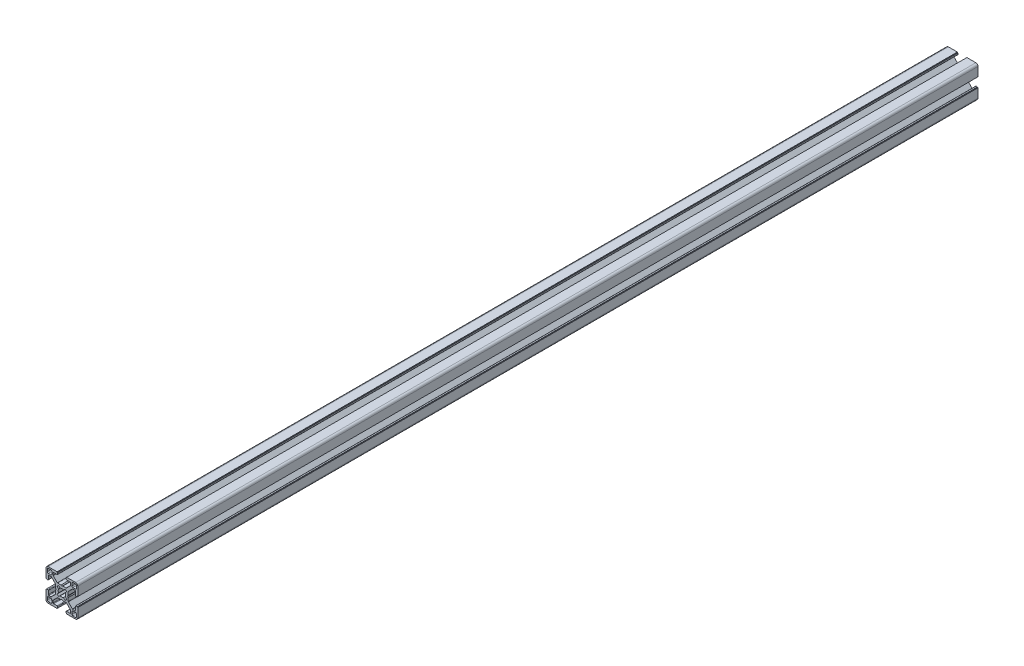
SolidWorks part; units mm, degrees
ref_plane "Front Plane" through (0, 0, 0) normal (0, 0, 1) x (1, 0, 0)
ref_plane "Top Plane" through (0, 0, 0) normal (0, 1, 0) x (1, 0, 0)
ref_plane "Right Plane" through (0, 0, 0) normal (1, 0, 0) x (0, 0, -1)
sketch "Sketch1" plane through (0, 0, 0) normal (0, 0, 1) x (1, 0, 0)
  line L0 (-15, 0) -> (15, 0) construction
  line L1 (0, -15) -> (0, 15) construction
  line L2 (-4.5, 15) -> (4.5, 15) construction
  line L3 (-4, -15) -> (4, -15) construction
  line L4 (-4.5, 15) -> (-4.5, 14.5)
  line L5 (-4.5, 14.5) -> (-4, 14.5)
  line L6 (-4, 14.5) -> (-4, 13.29)
  line L7 (-4.5, 12.79) -> (-7.7675, 12.79)
  line L8 (-8.2675, 12.29) -> (-8.2675, 10.2707)
  line L9 (-8.1211, 9.9171) -> (-4.3504, 6.1464)
  line L10 (-3.9968, 6) -> (0, 6)
  line L11 (0, 0) -> (-15, 15) construction
  line L12 (-4.5, 15) -> (-12.968, 15)
  line L14 (-12.705, 9.5135) -> (-10.5135, 9.5135)
  line L15 (-13.705, 10.5135) -> (-13.705, 12.705)
  line L16 (-12.705, 13.705) -> (-10.5135, 13.705)
  line L17 (-9.5135, 10.5135) -> (-9.5135, 12.705)
  line L18 (-13.705, 9.5135) -> (-9.5135, 13.705) construction
  line L19 (-13.705, 13.705) -> (-9.5135, 9.5135) construction
  line L20 (-3.1568, 4.5038) -> (-1.5303, 3.1477) construction
  line L21 (-4.5038, 3.1568) -> (-3.1477, 1.5303) construction
  line L22 (-6, 3.9968) -> (-6, 0)
  line L23 (-9.9171, 8.1211) -> (-6.1464, 4.3504)
  line L24 (-15, 4.5) -> (-15, 12.968)
  line L25 (-12.29, 8.2675) -> (-10.2707, 8.2675)
  line L26 (-12.79, 4.5) -> (-12.79, 7.7675)
  line L27 (-14.5, 4) -> (-13.29, 4)
  line L28 (-14.5, 4.5) -> (-14.5, 4)
  line L29 (-15, 4.5) -> (-14.5, 4.5)
  circle A0 centre (0, 0) radius 3.5
  arc A1 (-12.968, 15) -> (-15, 12.968) centre (-12.968, 12.968) ccw
  circle A2 centre (0, 0) radius 5.5 construction
  arc A3 (-10.5135, 9.5135) -> (-9.5135, 10.5135) centre (-10.5135, 10.5135) ccw
  arc A4 (-13.705, 12.705) -> (-12.705, 13.705) centre (-12.705, 12.705) cw
  arc A5 (-10.5135, 13.705) -> (-9.5135, 12.705) centre (-10.5135, 12.705) cw
  arc A6 (-12.705, 9.5135) -> (-13.705, 10.5135) centre (-12.705, 10.5135) cw
  arc A7 (-12.79, 4.5) -> (-13.29, 4) centre (-13.29, 4.5) cw
  arc A8 (-12.29, 8.2675) -> (-12.79, 7.7675) centre (-12.29, 7.7675) ccw
  arc A9 (-9.9171, 8.1211) -> (-10.2707, 8.2675) centre (-10.2707, 7.7675) ccw
  arc A10 (-6, 3.9968) -> (-6.1464, 4.3504) centre (-6.5, 3.9968) ccw
  arc A11 (-4.3504, 6.1464) -> (-3.9968, 6) centre (-3.9968, 6.5) ccw
  arc A12 (-4, 13.29) -> (-4.5, 12.79) centre (-4.5, 13.29) cw
  arc A13 (-7.7675, 12.79) -> (-8.2675, 12.29) centre (-7.7675, 12.29) ccw
  arc A14 (-8.2675, 10.2707) -> (-8.1211, 9.9171) centre (-7.7675, 10.2707) ccw
  point P4 (0, 0)
  point P8 (0, 0)
  point P13 (0, 15)
  point P15 (0, -15)
  point P16 (0, 6)
  point P23 (-11.6092, 11.6093)
  point P26 (0, 6)
  point P62 (-12.79, 4)
  point P65 (-12.79, 8.2675)
  point P68 (-10.0636, 8.2675)
  point P71 (-6, 4.2039)
  point P74 (-4.2039, 6)
  point P77 (-4, 12.79)
  point P80 (-8.2675, 12.79)
  point P83 (-8.2675, 10.0636)
  dimension "Center Hole Diameter" = 7
  dimension "D11" = 2.032
  dimension "D9" = 11
  dimension "D13" = 1
  dimension "D14" = 0.5
  dimension "Rail Height" = 30
  dimension "Rail Width" = 30
  dimension "T-Slot Width" = 8
  dimension "T-Slot Depth" = 9
  dimension "D1" = 9
  dimension "D2" = 45
  dimension "D3" = 8
  dimension "D4" = 2.21
  dimension "D5" = 16.535
  dimension "D7" = 2.54
  dimension "D6" = 1.295
  dimension "D8" = 1.246
  dimension "D10" = 10.36
  dimension "D12" = 1.905
sketch "Sketch2" plane through (0, 0, 0) normal (1, 0, 0) x (0, 0, -1)
  line L0 (-76.2, 0) -> (76.2, 0) construction
  line L2 (0, -15) -> (0, 15) construction
  line L3 (0, -15) -> (0, 15) construction
  line L4 (-76.2, -15) -> (-76.2, 15) construction
  line L5 (76.2, -15) -> (76.2, 15) construction
  point P0 (-38.7, 0)
  point P3 (0, 0)
  point P4 (38.7, 0)
  point P12 (-76.2, 0)
  point P14 (76.2, 0)
  dimension "Length" = 152.4
  dimension "D1" = 37.5
sketch "Sketch3" plane through (0, 0, 0) normal (0, 0, 1) x (1, 0, 0)
  line L0 (-4.5038, 3.1568) -> (-3.1477, 1.5303)
  line L1 (0, 3.5) -> (0, 5.5)
  line L2 (-5.5, 0) -> (-3.5, 0)
  line L7 (-6, 3.9968) -> (-6, 0) construction
  line L31 (-9.9171, 8.1211) -> (-6.1464, 4.3504) construction
  line L117 (-12.29, 8.2675) -> (-10.2707, 8.2675) construction
  line L118 (-12.79, 4.5) -> (-12.79, 7.7675) construction
  line L157 (-12.705, 9.5135) -> (-10.5135, 9.5135)
  line L158 (-9.5135, 10.5135) -> (-9.5135, 12.705)
  line L163 (-10.5135, 13.705) -> (-12.705, 13.705)
  line L164 (-13.705, 12.705) -> (-13.705, 10.5135)
  line L165 (-12.705, 9.5135) -> (-10.5135, 9.5135)
  line L166 (-9.5135, 10.5135) -> (-9.5135, 12.705)
  line L167 (-10.5135, 13.705) -> (-12.705, 13.705)
  line L168 (-13.705, 12.705) -> (-13.705, 10.5135)
  line L169 (-14.5, 4) -> (-13.29, 4) construction
  line L170 (-14.5, 4.5) -> (-14.5, 4) construction
  line L171 (-15, 4.5) -> (-14.5, 4.5) construction
  line L172 (-15, 4.5) -> (-15, 12.968) construction
  line L173 (-4.5, 15) -> (-12.968, 15) construction
  line L174 (-4.5, 15) -> (-4.5, 14.5) construction
  line L175 (-4.5, 14.5) -> (-4, 14.5) construction
  line L176 (-4, 14.5) -> (-4, 13.29) construction
  line L177 (-4.5, 12.79) -> (-7.7675, 12.79) construction
  line L178 (-8.2675, 12.29) -> (-8.2675, 10.2707) construction
  line L179 (-8.1211, 9.9171) -> (-4.3504, 6.1464) construction
  line L180 (-3.9968, 6) -> (0, 6) construction
  line L181 (-6, 3.9968) -> (-6, 0.866)
  line L182 (-9.9171, 8.1211) -> (-6.1464, 4.3504)
  line L183 (-12.29, 8.2675) -> (-10.2707, 8.2675)
  line L184 (-12.79, 4.5) -> (-12.79, 7.7675)
  line L185 (-14.5, 4) -> (-13.29, 4)
  line L186 (-14.5, 4.5) -> (-14.5, 4)
  line L187 (-15, 4.5) -> (-14.5, 4.5)
  line L188 (-15, 4.5) -> (-15, 12.968)
  line L189 (-4.5, 15) -> (-12.968, 15)
  line L190 (-4.5, 15) -> (-4.5, 14.5)
  line L191 (-4.5, 14.5) -> (-4, 14.5)
  line L192 (-4, 14.5) -> (-4, 13.29)
  line L193 (-4.5, 12.79) -> (-7.7675, 12.79)
  line L194 (-8.2675, 12.29) -> (-8.2675, 10.2707)
  line L195 (-8.1211, 9.9171) -> (-4.3504, 6.1464)
  line L196 (-3.9968, 6) -> (-0.866, 6)
  line L197 (-0.866, 6) -> (0, 5.5)
  line L198 (0, -15) -> (0, 15) construction
  line L199 (0, 0) -> (-15, 15) construction
  line L200 (0, 0) -> (-15, 15) construction
  line L201 (-3.1568, 4.5038) -> (-1.5303, 3.1477) construction
  line L202 (-3.1568, 4.5038) -> (-1.5303, 3.1477)
  line L203 (-6, 0.866) -> (-5.5, 0)
  line L204 (-15, 0) -> (15, 0) construction
  line L205 (-15, 0) -> (15, 0) construction
  line L206 (0, -15) -> (0, 15) construction
  arc A0 (-3.5, 0) -> (-3.1477, 1.5303) centre (0, 0) cw
  arc A10 (-6, 3.9968) -> (-6.1464, 4.3504) centre (-6.5, 3.9968) ccw construction
  circle A16 centre (0, 0) radius 3.5
  arc A18 (0, 3.5) -> (-1.5303, 3.1477) centre (0, 0) ccw
  arc A20 (-9.9171, 8.1211) -> (-10.2707, 8.2675) centre (-10.2707, 7.7675) ccw construction
  arc A22 (-12.29, 8.2675) -> (-12.79, 7.7675) centre (-12.29, 7.7675) ccw construction
  arc A28 (-13.29, 4) -> (-12.79, 4.5) centre (-13.29, 4.5) ccw construction
  arc A29 (-10.5135, 9.5135) -> (-9.5135, 10.5135) centre (-10.5135, 10.5135) ccw
  arc A30 (-9.5135, 12.705) -> (-10.5135, 13.705) centre (-10.5135, 12.705) ccw
  arc A31 (-12.705, 13.705) -> (-13.705, 12.705) centre (-12.705, 12.705) ccw
  arc A32 (-13.705, 10.5135) -> (-12.705, 9.5135) centre (-12.705, 10.5135) ccw
  arc A33 (-10.5135, 9.5135) -> (-9.5135, 10.5135) centre (-10.5135, 10.5135) ccw
  arc A34 (-9.5135, 12.705) -> (-10.5135, 13.705) centre (-10.5135, 12.705) ccw
  arc A35 (-12.705, 13.705) -> (-13.705, 12.705) centre (-12.705, 12.705) ccw
  arc A36 (-13.705, 10.5135) -> (-12.705, 9.5135) centre (-12.705, 10.5135) ccw
  arc A37 (-12.968, 15) -> (-15, 12.968) centre (-12.968, 12.968) ccw construction
  arc A38 (-4.5, 12.79) -> (-4, 13.29) centre (-4.5, 13.29) ccw construction
  arc A39 (-7.7675, 12.79) -> (-8.2675, 12.29) centre (-7.7675, 12.29) ccw construction
  arc A40 (-8.2675, 10.2707) -> (-8.1211, 9.9171) centre (-7.7675, 10.2707) ccw construction
  arc A41 (-4.3504, 6.1464) -> (-3.9968, 6) centre (-3.9968, 6.5) ccw construction
  arc A42 (-6, 3.9968) -> (-6.1464, 4.3504) centre (-6.5, 3.9968) ccw
  arc A43 (-9.9171, 8.1211) -> (-10.2707, 8.2675) centre (-10.2707, 7.7675) ccw
  arc A44 (-12.29, 8.2675) -> (-12.79, 7.7675) centre (-12.29, 7.7675) ccw
  arc A45 (-13.29, 4) -> (-12.79, 4.5) centre (-13.29, 4.5) ccw
  arc A46 (-12.968, 15) -> (-15, 12.968) centre (-12.968, 12.968) ccw
  arc A47 (-4.5, 12.79) -> (-4, 13.29) centre (-4.5, 13.29) ccw
  arc A48 (-7.7675, 12.79) -> (-8.2675, 12.29) centre (-7.7675, 12.29) ccw
  arc A49 (-8.2675, 10.2707) -> (-8.1211, 9.9171) centre (-7.7675, 10.2707) ccw
  arc A50 (-4.3504, 6.1464) -> (-3.9968, 6) centre (-3.9968, 6.5) ccw
  circle A51 centre (0, 0) radius 5.5 construction
  arc A52 (-3.1568, 4.5038) -> (-4.5038, 3.1568) centre (0, 0) ccw
  dimension "D3" = 60
  dimension "D4" = 60
  dimension "D1" = 0
  dimension "D2" = 0
extrude "Boss-Extrude1" add sketch "Sketch3" along normal mid plane 850
pattern_circular "CirPattern1" count 4 over 360 about axis through (0, 0, 76.2) along (0, 0, -1) of "Boss-Extrude1"
ref_plane "Contact Plane1" through (15, 0, 0) normal (1, 0, 0) x (0, 0, -1)
ref_plane "Contact Plane2" through (0, -15, 0) normal (0, 1, 0) x (1, 0, 0)
ref_plane "Contact Plane3" through (-15, 0, 0) normal (1, 0, 0) x (0, 0, -1)
ref_plane "Contact Plane4" through (0, 15, 0) normal (0, 1, 0) x (1, 0, 0)
equation "\"D1@Sketch2\" = \"Rail Height@Sketch1\" * 1.25"
equation "\"D1@Sketch1\"=\"T-Slot Width@Sketch1\"+1mm"
equation "\"D3@Sketch1\"=\"T-Slot Width@Sketch1\""
equation "\"D1@Boss-Extrude1\"=\"length\""
equation "\"length\" = 850"
